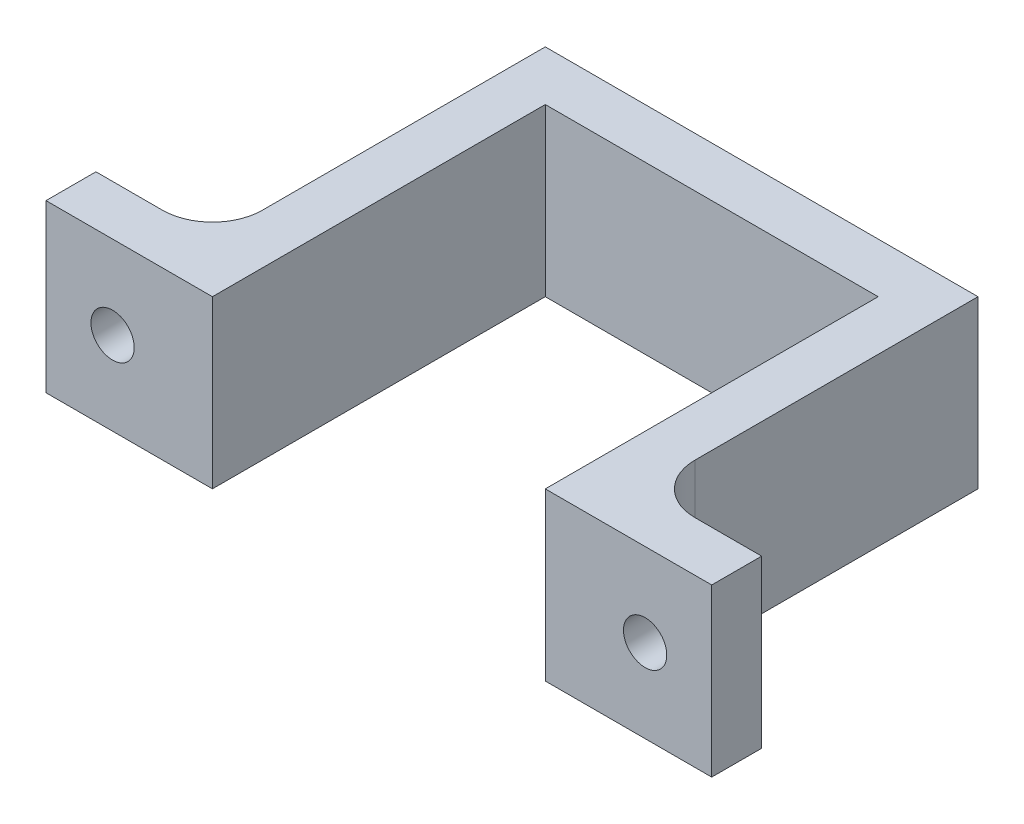
SolidWorks part; units mm, degrees
ref_plane "前视基准面" through (0, 0, 0) normal (0, 0, 1) x (1, 0, 0)
ref_plane "上视基准面" through (0, 0, 0) normal (0, 1, 0) x (1, 0, 0)
ref_plane "右视基准面" through (0, 0, 0) normal (1, 0, 0) x (0, 0, -1)
sketch "草图1" plane through (0, 0, 0) normal (0, 1, 0) x (1, 0, 0)
  line L1 (-20, 11.5) -> (20, 11.5)
  line L2 (-20, 11.5) -> (-20, -11.5)
  line L3 (-20, -11.5) -> (20, -11.5)
  line L4 (20, 11.5) -> (20, -11.5)
  line L5 (-20, 11.5) -> (20, -11.5) construction
  line L6 (-20, -11.5) -> (20, 11.5) construction
  point P0 (0, 0)
  dimension "D1" = 40
  dimension "D2" = 23
extrude "凸台-拉伸1" add sketch "草图1" along normal blind 10
sketch "草图2" plane through (0, 10, 0) normal (0, 1, 0) x (1, 0, 0)
  line L1 (-20, 11.5) -> (-13, 11.5)
  line L2 (-20, 11.5) -> (-20, -8.5)
  line L3 (-20, -8.5) -> (-13, -8.5)
  line L4 (-13, 11.5) -> (-13, -8.5)
  line L5 (20, 11.5) -> (13, 11.5)
  line L6 (20, 11.5) -> (20, -8.5)
  line L7 (20, -8.5) -> (13, -8.5)
  line L8 (13, 11.5) -> (13, -8.5)
  dimension "D1" = 20
  dimension "D2" = 20
  dimension "D3" = 7
  dimension "D4" = 7
extrude "切除-拉伸1" cut sketch "草图2" against normal blind 10
sketch "草图3" plane through (0, 10, 0) normal (0, 1, 0) x (1, 0, 0)
  line L0 (-20, -11.5) -> (20, -11.5) construction
  line L1 (-10, -11.5) -> (10, -11.5)
  line L2 (-10, -11.5) -> (-10, 8.5)
  line L3 (10, -11.5) -> (10, 8.5)
  line L4 (-10, 8.5) -> (10, 8.5)
  point P0 (10, -11.5)
  point P1 (-10, -11.5)
  point P4 (0, -11.5)
  dimension "D1" = 10
  dimension "D2" = 10
  dimension "D3" = 20
extrude "切除-拉伸2" cut sketch "草图3" against normal blind 10
sketch "草图4" plane through (0, 0, 8.5) normal (0, 0, -1) x (-1, 0, 0)
  line L0 (0, 10) -> (0, 0) construction
  line L1 (-13, 10) -> (13, 10) construction
  line L2 (-16, 5) -> (16, 5) construction
  circle A0 centre (16, 5) radius 1.3
  circle A1 centre (-16, 5) radius 1.3
  point P8 (0, 5)
  dimension "D1" = 32
extrude "切除-拉伸3" cut sketch "草图4" against normal blind 10
fillet "圆角1" radius 3 1 edges at (13, 5, 8.5)
fillet "圆角2" radius 3 1 edges at (-13, 5, 8.5)
